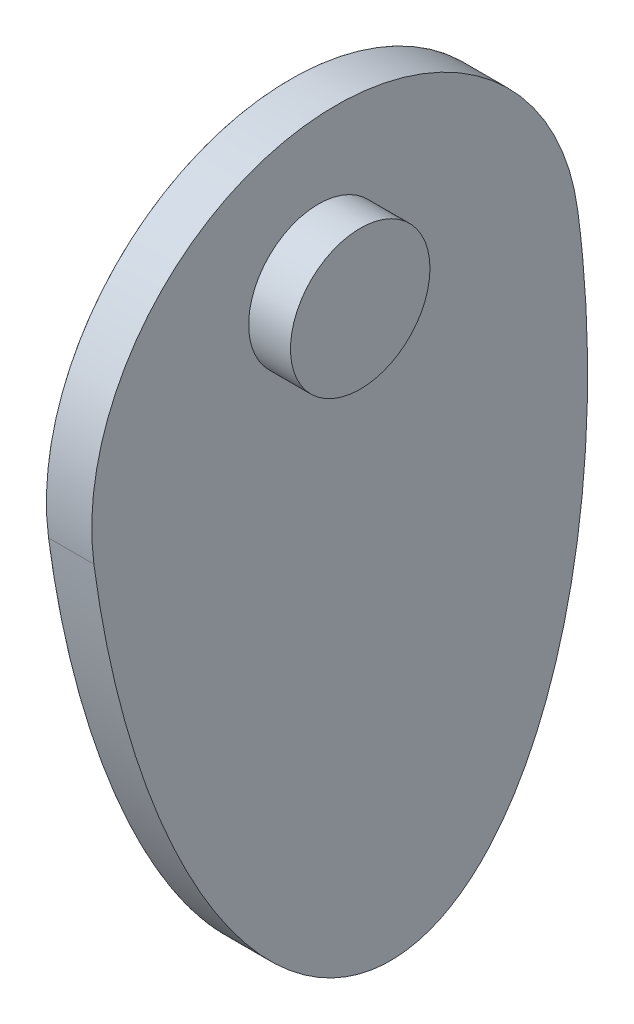
SolidWorks part; units mm, degrees
ref_plane "Plano frontal" through (0, 0, 0) normal (0, 0, 1) x (1, 0, 0)
ref_plane "Plano superior" through (0, 0, 0) normal (0, 1, 0) x (1, 0, 0)
ref_plane "Plano direito" through (0, 0, 0) normal (1, 0, 0) x (0, 0, -1)
sketch "Esboço43" plane through (0, 0, 0) normal (1, 0, 0) x (0, 0, -1)
  line L0 (0, 0) -> (0, -150) construction
  line L1 (0, -150) -> (20, -150) construction
  arc A0 (69.386, 9.2515) -> (-69.386, -9.2515) centre (0, 0) ccw
  ellipse E0 centre (0, 0) end of major axis (20, -150) minor radius 70 (-69.386, -9.2515) -> (69.386, 9.2515) ccw
  dimension "D1" = 140
  dimension "D2" = 150
  dimension "D3" = 20
extrude "Ressalto-extrusão11" add sketch "Esboço43" along normal blind 13
sketch3d "3DSketch4"
  arc A0 (13, 69.3586, 9.4543) -> (13, -149.9687, -20.2284) centre (-399.0364, -36.5209, -33.3487) cw
  arc A1 (13, 9.2515, -69.386) -> (13, -9.2515, 69.386) centre (13, 0, 0) ccw construction
  spline S0 degree 3 poles (13, -9.2515, 69.386) (13, -309.2515, 29.386) (13, -290.7485, -109.386) (13, 9.2515, -69.386) knots 0 0 0 0 1 1 1 1 weights 1 0.333333 0.333333 1 construction
  point P2 (-369.8245, 20.6877, -456.0665)
  point P8 (83, 0, 0)
surface "Superfície-Preenchimento3"
sketch "Esboço44" plane through (0, 0, 0) normal (1, 0, 0) x (0, 0, -1)
  line L0 (0, 70) -> (-25.8959, 70) construction
  circle A2 centre (-5, 28) radius 20
  spline S0 degree 3 poles (69.386, 9.2515) (69.3402, 9.5842) (69.2487, 10.2496) (69.0931, 11.2451) (68.9244, 12.2383) (68.741, 13.229) (68.5435, 14.217) (68.2109, 15.7648) (67.7009, 17.863) (66.9516, 20.4934) (65.8165, 23.9584) (64.1451, 28.2026) (62.1475, 32.3034) (59.9151, 36.2766) (56.9602, 40.8822) (53.5638, 45.1853) (49.234, 49.868) (45.2095, 53.5903) (40.8489, 56.8962) (37.0624, 59.4323) (33.1303, 61.7444) (29.0296, 63.7424) (24.8229, 65.4953) (20.5169, 67.0003) (16.1064, 68.1645) (11.6395, 69.0676) (7.1232, 69.7083) (2.5707, 69.9943) (-1.9867, 70.0133) (-7.4506, 69.7159) (-12.869, 68.8853) (-18.1923, 67.6377) (-22.565, 66.3386) (-26.8228, 64.7021) (-30.9737, 62.8208) (-35.011, 60.6977) (-38.8702, 58.266) (-42.5771, 55.6148) (-46.1256, 52.7486) (-49.4394, 49.6141) (-52.5613, 46.2939) (-56.0701, 42.0947) (-59.1579, 37.5653) (-61.8756, 32.821) (-64.3133, 27.9217) (-66.2647, 22.799) (-67.8063, 17.5533) (-68.8342, 13.109) (-69.5118, 8.5982) (-69.8414, 4.9669) (-69.9821, 2.2356) (-70.016, -0.4992) (-69.9434, -3.2333) (-69.7863, -5.6034) (-69.5935, -7.6093) (-69.4551, -8.7041) (-69.386, -9.2515) knots 0 0 0 0 0.004582 0.009165 0.013748 0.01833 0.022913 0.027495 0.039932 0.052369 0.064806 0.089675 0.114544 0.126981 0.15185 0.189142 0.201578 0.238871 0.263739 0.276177 0.301046 0.325914 0.338352 0.363221 0.38809 0.400527 0.425396 0.450265 0.462702 0.487571 0.524862 0.537299 0.562169 0.587037 0.599474 0.624344 0.649212 0.661649 0.686519 0.711387 0.723824 0.748694 0.785985 0.798423 0.823291 0.860583 0.87302 0.897889 0.922759 0.935195 0.947632 0.960069 0.972506 0.984943 0.992472 1 1 1 1 construction
  dimension "D1" = 40
  dimension "D3" = 42
  dimension "D2" = 5
  dimension "D4" = 70
extrude "Ressalto-extrusão12" add sketch "Esboço44" against normal blind 12
ref_plane "Plano1" through (-50, 0, 0) normal (1, 0, 0) x (0, 0, -1)
mirror "Espelhar3" about plane through (-50, 0, 0) normal (1, 0, 0) of bodies 118 117
delete or keep bodies "Corpo-Excluir/Manter 1" type delete bodies bodies 117 118
